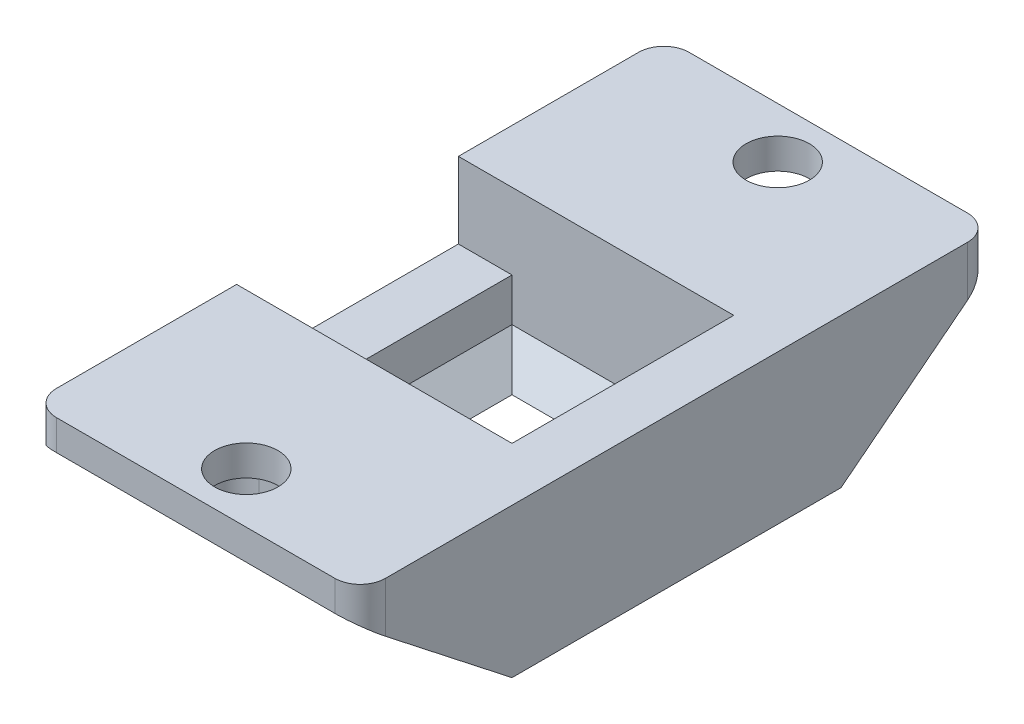
SolidWorks part; units mm, degrees
ref_plane "Front Plane" through (0, 0, 0) normal (0, 0, 1) x (1, 0, 0)
ref_plane "Top Plane" through (0, 0, 0) normal (0, 1, 0) x (1, 0, 0)
ref_plane "Right Plane" through (0, 0, 0) normal (1, 0, 0) x (0, 0, -1)
sketch "Sketch1" plane through (0, 0, 0) normal (0, 1, 0) x (1, 0, 0)
  line L1 (-4.3815, 4.3815) -> (4.3815, 4.3815)
  line L2 (-4.3815, 4.3815) -> (-4.3815, -4.3815)
  line L3 (-4.3815, -4.3815) -> (4.3815, -4.3815)
  line L4 (4.3815, 4.3815) -> (4.3815, -4.3815)
  line L5 (-4.3815, 4.3815) -> (4.3815, -4.3815) construction
  line L6 (-4.3815, -4.3815) -> (4.3815, 4.3815) construction
  line L7 (-2.8815, -2.8815) -> (2.8815, -2.8815)
  line L8 (-2.8815, -2.8815) -> (-2.8815, 2.8815)
  line L9 (-2.8815, 2.8815) -> (2.8815, 2.8815)
  line L10 (2.8815, -2.8815) -> (2.8815, 2.8815)
  line L11 (-2.8815, -2.8815) -> (2.8815, 2.8815) construction
  line L12 (-2.8815, 2.8815) -> (2.8815, -2.8815) construction
  point P0 (0, 0)
  point P6 (0, 0)
  dimension "D2" = 8.763
  dimension "D3" = 1.5
extrude "Boss-Extrude1" add sketch "Sketch1" along normal blind 1.2
sketch "Sketch2" plane through (0, 0, 0) normal (0, -1, 0) x (1, 0, 0)
  line L1 (-6.5, 6.5) -> (6.5, 6.5)
  line L2 (-6.5, 6.5) -> (-6.5, -6.5)
  line L3 (-6.5, -6.5) -> (6.5, -6.5)
  line L4 (4.3815, -4.3815) -> (4.3815, 4.3815)
  line L5 (4.3815, 4.3815) -> (-4.3815, 4.3815)
  line L6 (-4.3815, 4.3815) -> (-4.3815, -4.3815)
  line L7 (-4.3815, -4.3815) -> (4.3815, -4.3815)
  line L8 (4.3815, -4.3815) -> (4.3815, 4.3815)
  line L9 (4.3815, 4.3815) -> (-4.3815, 4.3815)
  line L10 (-4.3815, 4.3815) -> (-4.3815, -4.3815)
  line L11 (-4.3815, -4.3815) -> (4.3815, -4.3815)
  line L12 (6.5, 6.5) -> (6.5, -6.5)
  line L13 (-6.5, 6.5) -> (6.5, -6.5) construction
  line L14 (-6.5, -6.5) -> (6.5, 6.5) construction
  point P2 (0, 0)
  dimension "D2" = 13
  dimension "D1" = 0
extrude "Boss-Extrude3" add sketch "Sketch2" against normal offset from surface (5.9 mm away) 4.7 up to face at (0, 1.2, 0) offset beyond the face yes
chamfer "Chamfer1" distance 1.5 angle 45 4 edges at (0, 1.2, -2.8815) (2.8815, 1.2, 0) (0, 1.2, 2.8815) (-2.8815, 1.2, 0)
sketch "Sketch3" plane through (0, 5.9, 0) normal (0, 1, 0) x (1, 0, 0)
  line L0 (0, 6.5) -> (0, 12.5) construction
  line L1 (-6.5, 6.5) -> (6.5, 6.5)
  line L2 (-6.5, 6.5) -> (-6.5, 12.5)
  line L3 (-6.5, 12.5) -> (6.5, 12.5)
  line L4 (6.5, 6.5) -> (6.5, 12.5)
  circle A0 centre (0, 10.5) radius 1.25
  point P10 (0, 0)
  dimension "D3" = 2.5
  dimension "D1" = 10.5
  dimension "D2" = 12.5
extrude "Boss-Extrude4" add sketch "Sketch3" against normal blind 1.2
mirror "Mirror1" about plane through (0, 0, 0) normal (0, 0, 1) of "Boss-Extrude4"
sketch "Sketch5" plane through (-6.5, 0, 0) normal (-1, 0, 0) x (0, 0, 1)
  line L0 (6.5, 4.7) -> (6.5, 0) construction
  line L1 (12.5, 4.7) -> (6.5, 4.7) construction
  line L2 (-6.5, 4.7) -> (-6.5, 0) construction
  line L3 (-12.5, 4.7) -> (-6.5, 4.7) construction
  line L4 (6.5, 4.7) -> (6.5, 0)
  line L5 (12.5, 4.7) -> (6.5, 4.7)
  line L6 (-6.5, 4.7) -> (-6.5, 0)
  line L7 (-12.5, 4.7) -> (-6.5, 4.7)
  line L8 (12.5, 4.7) -> (6.5, 0)
  line L9 (-6.5, 0) -> (-12.5, 4.7)
extrude "Boss-Extrude5" add sketch "Sketch5" against normal blind 2
mirror "Mirror2" about plane through (0, 0, 0) normal (1, 0, 0) of "Boss-Extrude5"
fillet "Fillet1" radius 1 8 edges at (-4.5, 2.35, -6.5) (4.5, 2.35, 6.5) (4.5, 2.35, -6.5) (-6.5, 5.3, -12.5) (6.5, 5.3, -12.5) (-6.5, 5.3, 12.5) (6.5, 5.3, 12.5) (-4.5, 2.35, 6.5)
sketch "Sketch4" plane through (-6.5, 0, 0) normal (-1, 0, 0) x (0, 0, 1)
  line L0 (0, 0) -> (0, 5.9) construction
  line L1 (6.5, 0) -> (-6.5, 0) construction
  line L2 (11.5, 5.9) -> (-11.5, 5.9) construction
  line L4 (4.3815, 2.9) -> (-4.3815, 2.9)
  line L5 (4.3815, 2.9) -> (4.3815, 5.9)
  line L6 (4.3815, 5.9) -> (-4.3815, 5.9)
  line L7 (-4.3815, 2.9) -> (-4.3815, 5.9)
  line L8 (4.3815, 2.9) -> (-4.3815, 5.9) construction
  line L9 (4.3815, 5.9) -> (-4.3815, 2.9) construction
  point P6 (0, 4.4)
  dimension "D1" = 8.763
  dimension "D2" = 3
extrude "Cut-Extrude1" cut sketch "Sketch4" against normal up to next
